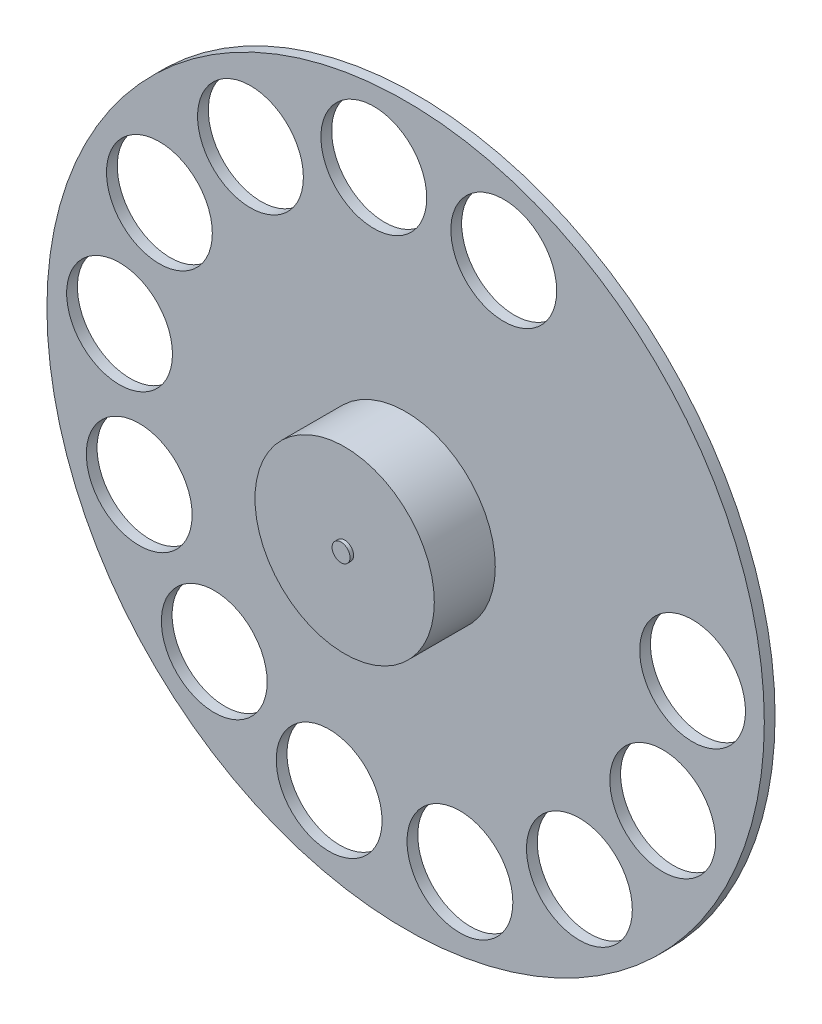
SolidWorks part; units mm, degrees
ref_plane "前视基准面" through (0, 0, 0) normal (0, 0, 1) x (1, 0, 0)
ref_plane "上视基准面" through (0, 0, 0) normal (0, 1, 0) x (1, 0, 0)
ref_plane "右视基准面" through (0, 0, 0) normal (1, 0, 0) x (0, 0, -1)
other "Configuration Table"
sketch "Sketch1" plane through (0, 0, 0) normal (0, 0, 1) x (1, 0, 0)
  circle A0 centre (0, 0) radius 100
  circle A1 centre (0, 0) radius 80
  circle A2 centre (80, 0) radius 14.75
  circle A3 centre (71.6795, -35.5253) radius 14.75
  circle A4 centre (48.4488, -63.6609) radius 14.75
  circle A5 centre (15.1401, -78.5543) radius 14.75
  circle A6 centre (-21.3179, -77.1074) radius 14.75
  circle A7 centre (-53.3415, -59.6212) radius 14.75
  circle A8 centre (-74.2694, -29.733) radius 14.75
  circle A9 centre (-79.7484, 6.34) radius 14.75
  circle A10 centre (-68.6387, 41.0942) radius 14.75
  circle A11 centre (-43.2513, 67.3003) radius 14.75
  circle A12 centre (-8.8671, 79.5071) radius 14.75
  circle A13 centre (27.3616, 75.1754) radius 14.75
  circle A14 centre (0, 0) radius 25
  point P30 (0, 0)
  dimension "D1" = 12
extrude "Boss-Extrude1" add sketch "Sketch1" along normal blind 3 contours A13 A1 A12 A11 A10 A9 A8 A7 A6 A5 A4 A3 A2 A14 | A0 A13 A1 A2 A3 A4 A5 A6 A7 A8 A9 A10 A11 A12 region at (-97.1716, 0, 0) region at (63.0015, 0, 0)
extrude "Boss-Extrude2" add sketch "Sketch1<3>" along normal blind 20 contours A14 region at (0, 0, 0)
sketch "Sketch1<3>" plane through (0, 0, 0) normal (0, 0, 1) x (1, 0, 0) same geometry as "Sketch1"
sketch "Sketch2" plane through (0, 0, 20) normal (0, 0, 1) x (1, 0, 0)
  circle A0 centre (0, 0) radius 2.5
extrude "Boss-Extrude3" add sketch "Sketch2" along normal blind 1
